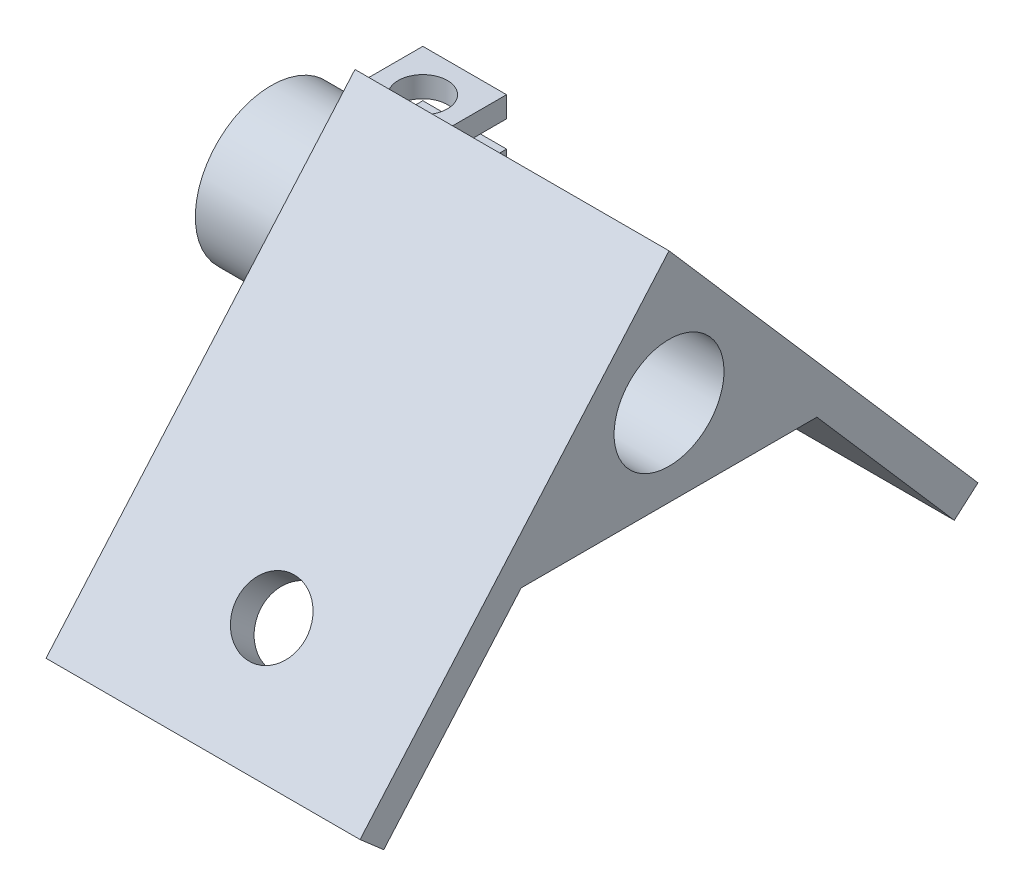
SolidWorks part; units mm, degrees
material "PLA Black"
ref_plane "Front" through (0, 0, 0) normal (0, 0, 1) x (1, 0, 0)
ref_plane "Top" through (0, 0, 0) normal (0, 1, 0) x (1, 0, 0)
ref_plane "Right" through (0, 0, 0) normal (1, 0, 0) x (0, 0, -1)
sketch "Sketch1" plane through (0, 0, 0) normal (1, 0, 0) x (0, 0, -1)
  line L0 (0, 12.5751) -> (-29.5132, -21.376)
  line L1 (-29.5132, -21.376) -> (-27.2491, -23.3442)
  line L2 (-27.2491, -23.3442) -> (-14.1279, -8.25)
  line L3 (-14.1279, -8.25) -> (14.1279, -8.25)
  line L4 (0, 31.2499) -> (0, -31.1028) construction
  line L5 (27.2491, -23.3442) -> (14.1279, -8.25)
  line L6 (0, 12.5751) -> (29.5132, -21.376)
  line L7 (29.5132, -21.376) -> (27.2491, -23.3442)
  circle A0 centre (0, 0) radius 5.25
  dimension "D1" = 10.5
  dimension "D4" = 3
  dimension "D2" = 41
  dimension "D3" = 3
  dimension "D5" = 3
  dimension "D6" = 20
extrude "Boss-Extrude1" add sketch "Sketch1" along normal mid plane 30
hole_wizard "M6 Clearance Hole1" positions "Sketch3" profile "Sketch4" hole size "M6" standard "DIN" end condition through all
sketch "Sketch3" plane through (0, 3.4443, 3.9622) normal (0, -0.6561, -0.7547) x (-1, 0, 0)
  line L0 (-34.564, -25.4951) -> (6.8322, -25.4951) construction
  line L2 (0, -15.4951) -> (0, -35.4951) construction
  line L3 (-15, -15.4951) -> (15, -15.4951) construction
  line L4 (-15, -35.4951) -> (15, -35.4951) construction
  point P0 (0, -25.4951)
sketch "Sketch4" plane through (0, -15.7971, 20.6885) normal (1, 0, 0) x (0, 0.7547, -0.6561)
  line L0 (0, 0) -> (0, 25.2739)
  line L1 (0, 25.2739) -> (3.3, 25.2739)
  line L2 (3.3, 25.2739) -> (3.3, 0)
  line L5 (3.3, 0) -> (0, 0)
  line L11 (0, -6.35) -> (0, 107.95) construction
  dimension "Thru Hole Dia." = 6.6
  dimension "Thru Hole Depth" = 25.2739
mirror "Mirror1" about plane through (0, 0, 0) normal (0, 0, 1) of "M6 Clearance Hole1"
sketch "Sketch5" plane through (-15, 0, 0) normal (-1, 0, 0) x (0, 0, 1)
  line L0 (-5.099, 1.25) -> (-14.4807, 1.25)
  line L1 (-14.4807, 1.25) -> (-14.4807, 3.25)
  line L2 (-14.4807, 3.25) -> (-6.4807, 3.25)
  line L3 (0, 0) -> (-16.2155, 0) construction
  line L4 (-6.4807, -3.25) -> (-6.4807, -10.25)
  line L5 (-14.4807, -1.25) -> (-14.4807, -10.25)
  line L6 (-5.099, -1.25) -> (-14.4807, -1.25)
  line L7 (-6.4807, -10.25) -> (-14.4807, -10.25)
  circle A0 centre (0, 0) radius 5.25 construction
  arc A1 (-6.4807, 3.25) -> (-6.4807, -3.25) centre (0, 0) cw
  arc A2 (-5.099, 1.25) -> (-5.099, -1.25) centre (0, 0) cw
  dimension "D1" = 2
  dimension "D2" = 8
  dimension "D3" = 2.5
  dimension "D4" = 2
  dimension "D5" = 9
extrude "Boss-Extrude2" add sketch "Sketch5" along normal blind 8
sketch "Sketch6" plane through (0, 3.25, 0) normal (0, 1, 0) x (1, 0, 0)
  line L0 (-19, 14.4807) -> (-19, 6.4807) construction
  line L1 (-23, 14.4807) -> (-15, 14.4807) construction
  line L2 (-23, 6.4807) -> (-15, 6.4807) construction
  circle A0 centre (-19, 10.4807) radius 2.35
  dimension "D1" = 4.7
extrude "Cut-Extrude1" cut sketch "Sketch6" against normal through all
